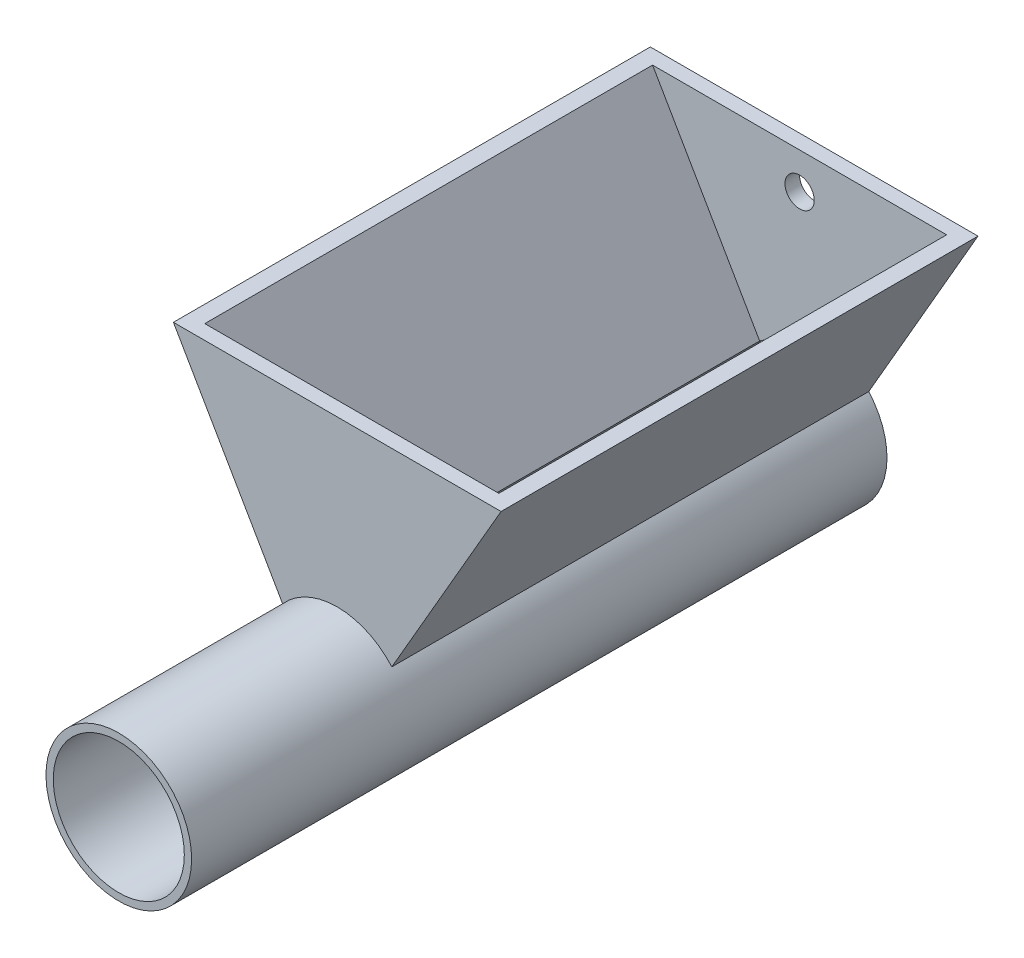
SolidWorks part; units mm, degrees
ref_plane "Front Plane" through (0, 0, 0) normal (0, 0, 1) x (1, 0, 0)
ref_plane "Top Plane" through (0, 0, 0) normal (0, 1, 0) x (1, 0, 0)
ref_plane "Right Plane" through (0, 0, 0) normal (1, 0, 0) x (0, 0, -1)
sketch "Sketch2" plane through (0, 0, 0) normal (0, 0, 1) x (1, 0, 0)
  line L0 (9.525, 8.4003) -> (28.575, 41.3958)
  line L1 (28.575, 41.3958) -> (-28.575, 41.3958)
  line L2 (-28.575, 41.3958) -> (-9.525, 8.4003)
  line L3 (55, 0) -> (-55, 0) construction
  arc A0 (-9.525, 8.4003) -> (9.525, 8.4003) centre (0, 0) ccw
  dimension "D1" = 25.4
  dimension "D2" = 38.1
  dimension "D3" = 120
  dimension "D4" = 120
  dimension "D5" = 57.15
extrude "Boss-Extrude1" add sketch "Sketch2" along normal mid plane 83.185
shell "Shell1" thickness 2.54 removed face at (0, 41.3958, 0)
sketch "Sketch3" plane through (0, 0, 41.5925) normal (0, 0, 1) x (1, 0, 0)
  circle A0 centre (0, 0) radius 12.7
  dimension "D1" = 25.4
extrude "Boss-Extrude2" add sketch "Sketch3" along normal blind 38.1
sketch "Sketch4" plane through (0, 0, 79.6925) normal (0, 0, 1) x (1, 0, 0)
  circle A0 centre (0, 0) radius 11.43
  dimension "D1" = 22.86
extrude "Cut-Extrude1" cut sketch "Sketch4" against normal through all
sketch "Sketch18" plane through (0, 0, 41.5925) normal (0, 0, 1) x (1, 0, 0)
  line L0 (0, 41.3958) -> (0, 35.0458) construction
  line L1 (28.575, 41.3958) -> (-28.575, 41.3958) construction
  dimension "D1" = 6.35
hole_wizard "1/4-20 Tapped Hole1" positions "Sketch19" profile "Sketch20" tap size "1/4-20" standard "ANSI Inch" end condition up to next
sketch "Sketch19" plane through (0, 0, -41.5925) normal (0, 0, 1) x (1, 0, 0)
  point P0 (0, 35.0458)
sketch "Sketch20" plane through (0, 35.0458, -41.5925) normal (1, 0, 0) x (0, 1, 0)
  line L0 (0, 0) -> (0, 2.54)
  line L1 (0, 2.54) -> (2.5527, 2.54)
  line L2 (2.5527, 2.54) -> (2.5527, 0)
  line L5 (2.5527, 0) -> (0, 0)
  line L11 (0, -6.35) -> (0, 107.95) construction
  dimension "Thru Tap Drill Dia." = 5.1054
  dimension "Thru Tap Drill Depth" = 2.54
cosmetic thread "Hole Thread1" parameters "D2"=6.35
